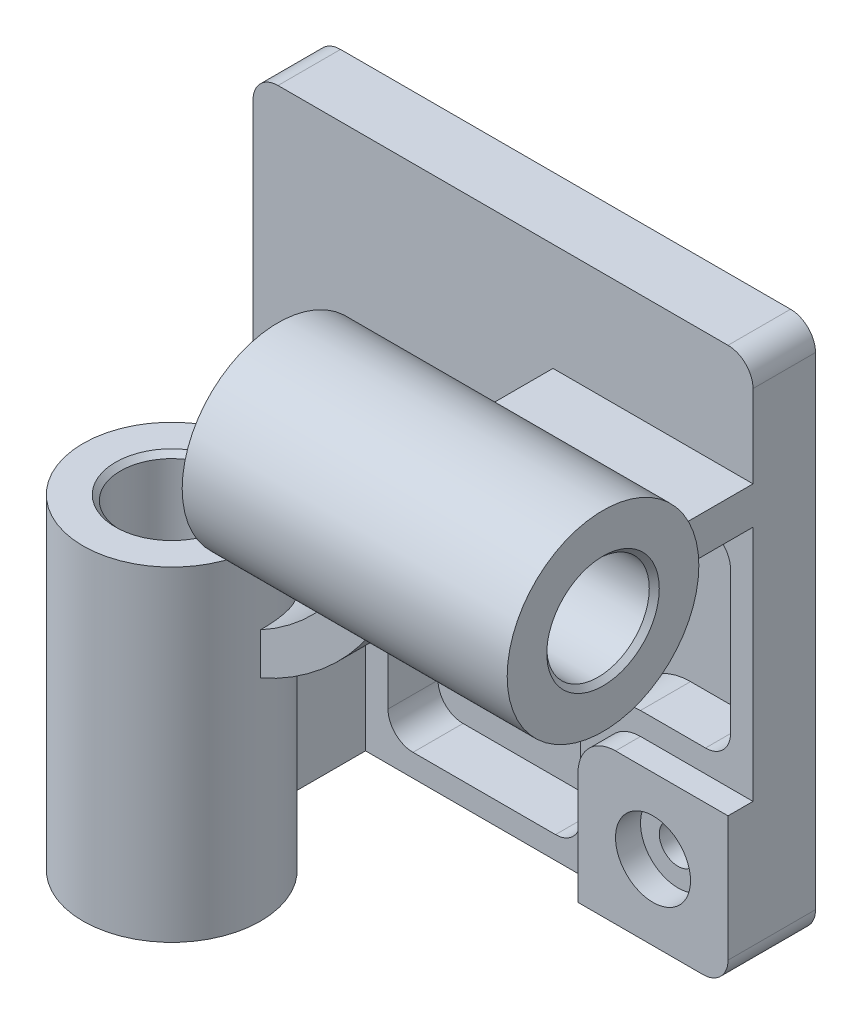
SolidWorks part; units mm, degrees
material "Alloy Steel"
ref_plane "Front Plane" through (0, 0, 0) normal (0, 0, 1) x (1, 0, 0)
ref_plane "Top Plane" through (0, 0, 0) normal (0, 1, 0) x (1, 0, 0)
ref_plane "Right Plane" through (0, 0, 0) normal (1, 0, 0) x (0, 0, -1)
sketch "Sketch2" plane through (0, 0, 0) normal (0, 0, 1) x (1, 0, 0)
  line L0 (30, 0) -> (30, 80)
  line L1 (10, 0) -> (190, 0)
  line L2 (0, 10) -> (0, 203)
  line L3 (10, 213) -> (190, 213)
  line L4 (200, 10) -> (200, 203)
  line L5 (200, 170) -> (120, 170)
  line L6 (200, 60) -> (155, 60)
  line L7 (140, 45) -> (140, 0)
  line L8 (200, 155) -> (133.923, 155)
  line L9 (45, 0) -> (45, 66.077)
  arc A0 (10, 0) -> (0, 10) centre (10, 10) cw
  arc A1 (190, 0) -> (200, 10) centre (190, 10) ccw
  arc A2 (190, 213) -> (200, 203) centre (190, 203) cw
  arc A3 (0, 203) -> (10, 213) centre (10, 203) cw
  arc A4 (120, 170) -> (30, 80) centre (30, 170) cw
  arc A5 (155, 60) -> (140, 45) centre (155, 45) ccw
  arc A6 (133.923, 155) -> (45, 66.077) centre (30, 170) cw
  point P7 (0, 0)
  point P10 (200, 0)
  point P15 (0, 213)
  point P26 (140, 60)
  dimension "D3" = 10
  dimension "D8" = 15
  dimension "D1" = 213
  dimension "D2" = 200
  dimension "D4" = 80
  dimension "D5" = 80
  dimension "D6" = 60
  dimension "D7" = 60
  dimension "D10" = 170
  dimension "D11" = 170
  dimension "D9" = 15
extrude "Boss-Extrude1" add sketch "Sketch2" along normal blind 25 contours A4 L5 L4 A2 L3 A3 L2 A0 L1 L0 | L8 A6 L9 L1 L7 A5 L6 L4 region at (68.3097, 145.5093, 0) region at (127.0973, 72.9027, 0)
extrude "Boss-Extrude2" add sketch "Sketch2<3>" along normal blind 35 contours L6 A5 L7 L1 A1 L4 region at (170.1957, 29.8043, 0)
sketch "Sketch2<3>" plane through (0, 0, 0) normal (0, 0, 1) x (1, 0, 0) same geometry as "Sketch2"
extrude "Boss-Extrude3" add sketch "Sketch2<4>" along normal blind 95 contours A6 L8 L4 L5 A4 L0 L1 L9 region at (96.9024, 103.0976, 0)
sketch "Sketch2<4>" plane through (0, 0, 0) normal (0, 0, 1) x (1, 0, 0) same geometry as "Sketch2"
sketch "Sketch3" plane through (200, 0, 0) normal (1, 0, 0) x (0, 0, -1)
  line L0 (-95, 155) -> (-95, 170) construction
  circle A0 centre (-95, 162.5) radius 38.335
  dimension "76.67" = 76.67
extrude "Boss-Extrude4" add sketch "Sketch3" against normal blind 130 from offset 10
sketch "Sketch4" plane through (0, 0, 0) normal (0, -1, 0) x (1, 0, 0)
  line L0 (30, 95) -> (45, 95) construction
  circle A0 centre (37.5, 95) radius 35.5
  dimension "D1" = 71
extrude "Boss-Extrude5" add sketch "Sketch4" against normal blind 130 from offset 10
sketch "Sketch5" plane through (0, -10, 0) normal (0, -1, 0) x (1, 0, 0)
  circle A0 centre (37.5, 95) radius 20.5
  dimension "D1" = 41
extrude "Cut-Extrude1" cut sketch "Sketch5" against normal through all
sketch "Sketch6" plane through (210, 0, 0) normal (1, 0, 0) x (0, 0, -1)
  circle A0 centre (-95, 162.5) radius 20.5
  dimension "D1" = 41
extrude "Cut-Extrude2" cut sketch "Sketch6" against normal through all
sketch "Sketch8" plane through (0, 0, 25) normal (0, 0, 1) x (1, 0, 0)
  line L12 (191, 146) -> (141.4451, 146)
  line L13 (54, 58.5549) -> (54, 9)
  line L14 (54, 9) -> (131, 9)
  line L15 (131, 9) -> (131, 45)
  line L16 (155, 69) -> (191, 69)
  line L17 (191, 69) -> (191, 146)
  line L18 (191, 146) -> (141.4451, 146)
  line L19 (54, 58.5549) -> (54, 9)
  line L20 (54, 9) -> (131, 9)
  line L21 (131, 9) -> (131, 45)
  line L22 (155, 69) -> (191, 69)
  line L23 (191, 69) -> (191, 146)
  arc A4 (54, 58.5549) -> (141.4451, 146) centre (30, 170) ccw
  arc A5 (155, 69) -> (131, 45) centre (155, 45) ccw
  arc A6 (54, 58.5549) -> (141.4451, 146) centre (30, 170) ccw
  arc A7 (155, 69) -> (131, 45) centre (155, 45) ccw
  dimension "D1" = 9
extrude "Cut-Extrude7" cut sketch "Sketch8" against normal offset from surface (20 mm away) 5 contours L21 A7 L22 L23 L18 A6 L19 L20 up to face at (100, 106.5, 0)
fillet "Fillet1" radius 10 6 edges at (131, 9, 15) (191, 69, 15) (191, 146, 15) (54, 58.5549, 15) (54, 9, 15) (141.4451, 146, 15)
hole_wizard "CBORE for M8 Hex Head Bolt1" positions "3DSketch2" profile "Sketch9" counterbore size "M8" standard "ANSI Metric" end condition through all
sketch3d "3DSketch2"
  line L0 (200, 10, 35) -> (200, 60, 35) construction
  line L1 (140, 0, 35) -> (190, 0, 35) construction
  point P0 (170, 30, 35)
  dimension "D1" = 30
  dimension "D2" = 30
sketch "Sketch9" plane through (170, 30, 35) normal (1, 0, 0) x (0, -1, 0)
  line L0 (0, 0) -> (0, 35)
  line L1 (0, 35) -> (7.5, 35)
  line L3 (7.5, 35) -> (7.5, 10)
  line L4 (7.5, 10) -> (15, 10)
  line L5 (15, 10) -> (15, 0)
  line L7 (15, 0) -> (0, 0)
  line L11 (0, -6.35) -> (0, 107.95) construction
  dimension "Thru Hole Dia." = 15
  dimension "Thru Hole Depth" = 35
  dimension "C'Bore Dia." = 30
  dimension "C'Bore Depth" = 10
chamfer "Chamfer1" distance 2 angle 45 4 edges at (80, 162.5, 74.5) (210, 162.5, 74.5) (37.5, 120, 74.5) (37.5, -10, 74.5)
